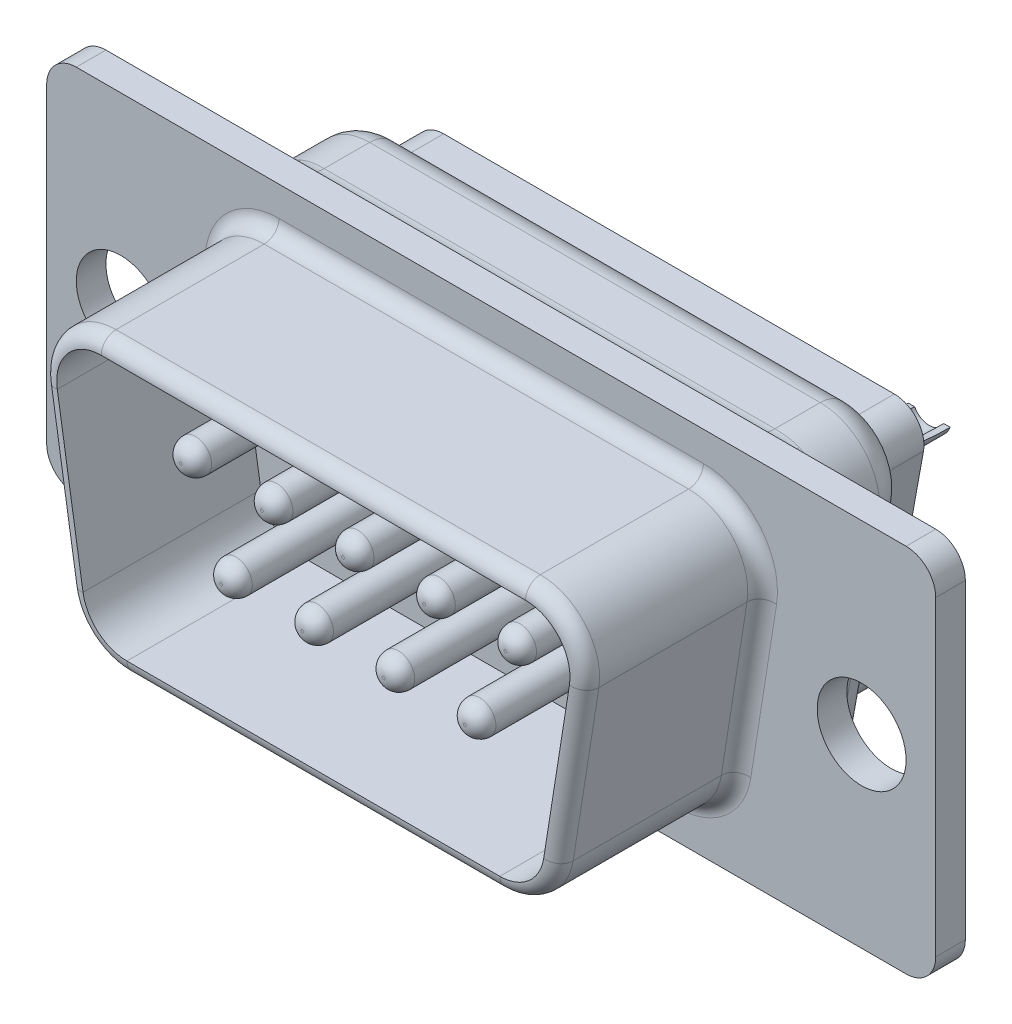
SolidWorks part; units mm, degrees
ref_plane "Спереди" through (0, 0, 0) normal (0, 0, 1) x (1, 0, 0)
ref_plane "Сверху" through (0, 0, 0) normal (0, 1, 0) x (1, 0, 0)
ref_plane "Справа" through (0, 0, 0) normal (1, 0, 0) x (0, 0, -1)
sketch "Эскиз1" plane through (0, 0, 0) normal (0, 0, 1) x (1, 0, 0)
  line L1 (-15, 6.25) -> (15, 6.25)
  line L2 (-15, 6.25) -> (-15, -6.25)
  line L3 (-15, -6.25) -> (15, -6.25)
  line L4 (15, 6.25) -> (15, -6.25)
  line L5 (-15, 6.25) -> (15, -6.25) construction
  line L6 (-15, -6.25) -> (15, 6.25) construction
  point P0 (0, 0)
  dimension "D1" = 30
  dimension "D2" = 12.5
extrude "Бобышка-Вытянуть1" add sketch "Эскиз1" along normal mid plane 1
sketch "Эскиз2" plane through (0, 0, -0.5) normal (0, 0, -1) x (-1, 0, 0)
  line L0 (0, 5.5) -> (0, -5.5) construction
  line L1 (-7.6036, 5.5) -> (7.6036, 5.5)
  line L2 (-9.5713, 3.1422) -> (-8.2986, -3.8578)
  line L3 (-6.3308, -5.5) -> (6.3308, -5.5)
  line L4 (9.5713, 3.1422) -> (8.2986, -3.8578)
  arc A0 (6.3308, -5.5) -> (8.2986, -3.8578) centre (6.3308, -3.5) ccw
  arc A1 (-8.2986, -3.8578) -> (-6.3308, -5.5) centre (-6.3308, -3.5) ccw
  arc A2 (7.6036, 5.5) -> (9.5713, 3.1422) centre (7.6036, 3.5) cw
  arc A3 (-7.6036, 5.5) -> (-9.5713, 3.1422) centre (-7.6036, 3.5) ccw
  point P0 (0, 0)
  point P10 (8, -5.5)
  point P13 (-8, -5.5)
  point P16 (10, 5.5)
  point P19 (-10, 5.5)
  dimension "D4" = 2
  dimension "D1" = 11
  dimension "D2" = 20
  dimension "D3" = 16
extrude "Бобышка-Вытянуть2" add sketch "Эскиз2" along normal blind 3.5
sketch "Эскиз3" plane through (0, 0, -4) normal (0, 0, -1) x (-1, 0, 0)
  line L0 (7.3147, -3.6789) -> (8.5874, 3.3211)
  line L1 (7.6036, 4.5) -> (-7.6036, 4.5)
  line L2 (-8.5874, 3.3211) -> (-7.3147, -3.6789)
  line L3 (-6.3308, -4.5) -> (6.3308, -4.5)
  line L4 (8.2986, -3.8578) -> (9.5713, 3.1422)
  line L5 (7.6036, 5.5) -> (-7.6036, 5.5)
  line L6 (-9.5713, 3.1422) -> (-8.2986, -3.8578)
  line L7 (-6.3308, -5.5) -> (6.3308, -5.5)
  line L8 (8.2986, -3.8578) -> (9.5713, 3.1422) construction
  line L9 (7.6036, 5.5) -> (-7.6036, 5.5) construction
  line L10 (-9.5713, 3.1422) -> (-8.2986, -3.8578) construction
  line L11 (-6.3308, -5.5) -> (6.3308, -5.5) construction
  arc A0 (8.5874, 3.3211) -> (7.6036, 4.5) centre (7.6036, 3.5) ccw
  arc A1 (-7.6036, 4.5) -> (-8.5874, 3.3211) centre (-7.6036, 3.5) ccw
  arc A2 (-7.3147, -3.6789) -> (-6.3308, -4.5) centre (-6.3308, -3.5) ccw
  arc A3 (6.3308, -4.5) -> (7.3147, -3.6789) centre (6.3308, -3.5) ccw
  arc A4 (6.3308, -5.5) -> (8.2986, -3.8578) centre (6.3308, -3.5) ccw
  arc A5 (9.5713, 3.1422) -> (7.6036, 5.5) centre (7.6036, 3.5) ccw
  arc A6 (-7.6036, 5.5) -> (-9.5713, 3.1422) centre (-7.6036, 3.5) ccw
  arc A7 (-8.2986, -3.8578) -> (-6.3308, -5.5) centre (-6.3308, -3.5) ccw
  arc A8 (6.3308, -5.5) -> (8.2986, -3.8578) centre (6.3308, -3.5) ccw construction
  arc A9 (9.5713, 3.1422) -> (7.6036, 5.5) centre (7.6036, 3.5) ccw construction
  arc A10 (-7.6036, 5.5) -> (-9.5713, 3.1422) centre (-7.6036, 3.5) ccw construction
  arc A11 (-8.2986, -3.8578) -> (-6.3308, -5.5) centre (-6.3308, -3.5) ccw construction
  dimension "D1" = 0
  dimension "D2" = 1
extrude "Бобышка-Вытянуть3" add sketch "Эскиз3" along normal blind 1.5
sketch "Эскиз4" plane through (0, 0, -5.5) normal (0, 0, -1) x (-1, 0, 0)
  circle A0 centre (-5.48, 1.42) radius 0.75
  circle A1 centre (-5.48, 1.42) radius 0.55
  dimension "D1" = 1.5
  dimension "D2" = 0.2
  dimension "D4" = 5.48
  dimension "D3" = 1.42
extrude "Бобышка-Вытянуть4" add sketch "Эскиз4" along normal blind 3.3
sketch "Эскиз5" plane through (0, 0, 0) normal (1, 0, 0) x (0, 0, -1)
  line L0 (8.8, 0.67) -> (8.8, 2.17) construction
  ellipse E0 centre (8.8, 2.17) end of major axis (11.3, 2.17) minor radius 1
  dimension "D1" = 2.5
  dimension "D2" = 1
extrude "Вырез-Вытянуть1" cut sketch "Эскиз5" along normal through all
pattern_linear "Линейный массив1" count 5 spacing 2.74 along (-1, 0, 0) of "Бобышка-Вытянуть4", "Вырез-Вытянуть1"
sketch "Эскиз6" plane through (0, 0, -5.5) normal (0, 0, -1) x (-1, 0, 0)
  circle A0 centre (-4.11, -1.42) radius 0.75
  circle A1 centre (-4.11, -1.42) radius 0.55
  circle A2 centre (-5.48, 1.42) radius 0.75 construction
  circle A3 centre (-5.48, 1.42) radius 0.55 construction
  dimension "D1" = 1.42
  dimension "D2" = 4.11
extrude "Бобышка-Вытянуть5" add sketch "Эскиз6" along normal blind 3.3
sketch "Эскиз7" plane through (0, 0, 0) normal (1, 0, 0) x (0, 0, -1)
  line L0 (8.8, -2.17) -> (8.8, -0.67) construction
  ellipse E0 centre (8.8, -2.17) end of major axis (6.3, -2.17) minor radius 1
  dimension "D1" = 1
extrude "Вырез-Вытянуть2" cut sketch "Эскиз7" along normal through all
pattern_linear "Линейный массив2" count 4 spacing 2.74 along (-1, 0, 0) of "Бобышка-Вытянуть5", "Вырез-Вытянуть2"
sketch "Эскиз8" plane through (0, 0, 0.5) normal (0, 0, 1) x (1, 0, 0)
  line L0 (-12.5, 0) -> (12.5, 0) construction
  circle A0 centre (-12.5, 0) radius 1.5
  circle A1 centre (12.5, 0) radius 1.5
  dimension "D2" = 3
  dimension "D1" = 25
extrude "Вырез-Вытянуть3" cut sketch "Эскиз8" against normal through all
fillet "Скругление1" radius 1 4 edges at (15, -6.25, 0) (-15, -6.25, 0) (-15, 6.25, 0) (15, 6.25, 0)
fillet "Скругление2" radius 1 14 edges at (9.1391, 4.7815, -4) (0, 5.5, -4) (-9.1391, 4.7815, -4) (-8.935, -0.3578, -4) (-7.6123, -5.0355, -4) (0, -5.5, -4) (7.6123, -5.0355, -4) (-9.1391, 4.7815, -0.5) (-8.935, -0.3578, -0.5) (-7.6123, -5.0355, -0.5) (7.6123, -5.0355, -0.5) (8.935, -0.3578, -0.5) (9.1391, 4.7815, -0.5) (8.935, -0.3578, -4)
sketch "Эскиз9" plane through (0, 0, 0.5) normal (0, 0, 1) x (1, 0, 0)
  line L0 (0, 4.75) -> (0, -4.75) construction
  line L1 (-7.1594, 4.75) -> (7.1594, 4.75)
  line L2 (-9.135, 2.4381) -> (-8.2665, -3.0619)
  line L3 (-6.291, -4.75) -> (6.291, -4.75)
  line L4 (9.135, 2.4381) -> (8.2665, -3.0619)
  line L5 (-7.1594, 4.25) -> (7.1594, 4.25)
  line L6 (8.6411, 2.5161) -> (7.7727, -2.9839)
  line L7 (-6.291, -4.25) -> (6.291, -4.25)
  line L8 (-8.6411, 2.5161) -> (-7.7727, -2.9839)
  arc A0 (6.291, -4.75) -> (8.2665, -3.0619) centre (6.291, -2.75) ccw
  arc A1 (-8.2665, -3.0619) -> (-6.291, -4.75) centre (-6.291, -2.75) ccw
  arc A2 (7.1594, 4.75) -> (9.135, 2.4381) centre (7.1594, 2.75) cw
  arc A3 (-7.1594, 4.75) -> (-9.135, 2.4381) centre (-7.1594, 2.75) ccw
  arc A4 (7.1594, 4.25) -> (8.6411, 2.5161) centre (7.1594, 2.75) cw
  arc A5 (6.291, -4.25) -> (7.7727, -2.9839) centre (6.291, -2.75) ccw
  arc A6 (-7.7727, -2.9839) -> (-6.291, -4.25) centre (-6.291, -2.75) ccw
  arc A7 (-7.1594, 4.25) -> (-8.6411, 2.5161) centre (-7.1594, 2.75) ccw
  point P0 (0, 0)
  point P10 (8, -4.75)
  point P13 (-8, -4.75)
  point P16 (9.5, 4.75)
  point P19 (-9.5, 4.75)
  dimension "D4" = 2
  dimension "D1" = 19
  dimension "D2" = 16
  dimension "D3" = 9.5
  dimension "D5" = 0.5
extrude "Бобышка-Вытянуть6" add sketch "Эскиз9" along normal blind 6
sketch "Эскиз10" plane through (0, 0, 0.5) normal (0, 0, 1) x (1, 0, 0)
  circle A0 centre (5.48, 1.42) radius 0.55
  circle A1 centre (2.74, 1.42) radius 0.55
  circle A2 centre (0, 1.42) radius 0.55
  circle A3 centre (-2.74, 1.42) radius 0.55
  circle A4 centre (-5.48, 1.42) radius 0.55
  circle A5 centre (-4.11, -1.42) radius 0.55
  circle A6 centre (-1.37, -1.42) radius 0.55
  circle A7 centre (1.37, -1.42) radius 0.55
  circle A8 centre (4.11, -1.42) radius 0.55
  circle A9 centre (5.48, 1.42) radius 0.55 construction
extrude "Бобышка-Вытянуть7" add sketch "Эскиз10" along normal blind 5
fillet "Скругление3" radius 0.5 25 edges at (8.6799, 4.0493, 6.5) (8.7007, -0.3119, 6.5) (7.5903, -4.2705, 6.5) (0, -4.75, 6.5) (-7.5903, -4.2705, 6.5) (-8.7007, -0.3119, 6.5) (-8.6799, 4.0493, 6.5) (8.6799, 4.0493, 0.5) (8.7007, -0.3119, 0.5) (7.5903, -4.2705, 0.5) (0, -4.75, 0.5) (-7.5903, -4.2705, 0.5) (-8.7007, -0.3119, 0.5) (-8.6799, 4.0493, 0.5) (4.66, -1.42, 5.5) (1.92, -1.42, 5.5) (-0.82, -1.42, 5.5) (-3.56, -1.42, 5.5) (6.03, 1.42, 5.5) (3.29, 1.42, 5.5) (0.55, 1.42, 5.5) (-2.19, 1.42, 5.5) (-4.93, 1.42, 5.5) (0, 4.75, 6.5) (0, 4.75, 0.5)
